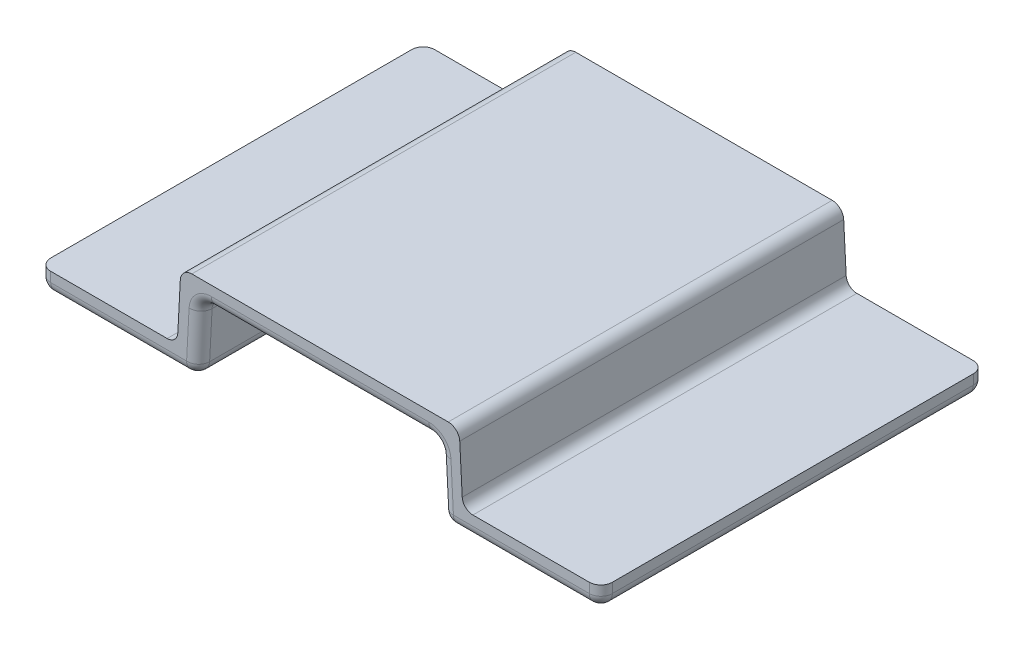
SolidWorks part; units mm, degrees
ref_plane "Front Plane" through (0, 0, 0) normal (0, 0, 1) x (1, 0, 0)
ref_plane "Top Plane" through (0, 0, 0) normal (0, 1, 0) x (1, 0, 0)
ref_plane "Right Plane" through (0, 0, 0) normal (1, 0, 0) x (0, 0, -1)
sketch "Sketch1" plane through (0, 0, 0) normal (0, 0, 1) x (1, 0, 0)
  line L0 (-329.1, -55) -> (-329.1, -80)
  line L1 (-329.1, -80) -> (-156.3657, -80)
  line L2 (-142.8842, -67.2065) -> (-139.9829, -11.8458)
  line L3 (-127.5, 0) -> (127.5, 0)
  line L4 (-329.1, -55) -> (-179.1409, -55)
  line L5 (-166.658, -43.1542) -> (-163.7566, 12.2065)
  line L6 (-150.2751, 25) -> (150.2751, 25)
  line L8 (0, 54.7842) -> (0, -49.5051) construction
  line L9 (166.658, -43.1542) -> (163.7566, 12.2065)
  line L10 (329.1, -55) -> (179.1409, -55)
  line L11 (142.8842, -67.2065) -> (139.9829, -11.8458)
  line L12 (329.1, -80) -> (156.3657, -80)
  line L13 (329.1, -55) -> (329.1, -80)
  arc A0 (-156.3657, -80) -> (-142.8842, -67.2065) centre (-156.3657, -66.5) ccw
  arc A1 (-179.1409, -55) -> (-166.658, -43.1542) centre (-179.1409, -42.5) ccw
  arc A2 (-163.7566, 12.2065) -> (-150.2751, 25) centre (-150.2751, 11.5) cw
  arc A4 (139.9829, -11.8458) -> (127.5, 0) centre (127.5, -12.5) ccw
  arc A5 (163.7566, 12.2065) -> (150.2751, 25) centre (150.2751, 11.5) ccw
  arc A6 (179.1409, -55) -> (166.658, -43.1542) centre (179.1409, -42.5) cw
  arc A7 (156.3657, -80) -> (142.8842, -67.2065) centre (156.3657, -66.5) cw
  arc A8 (-139.9829, -11.8458) -> (-127.5, 0) centre (-127.5, -12.5) cw
  point P9 (0, 25)
  point P10 (0, 0)
  dimension "D7" = 13.5
  dimension "D8" = 12.5
  dimension "D9" = 13.5
  dimension "D11" = 25
  dimension "D2" = 12.5
  dimension "D12" = 12.5
  dimension "D1" = 25
  dimension "D3" = 25
  dimension "D4" = 93
  dimension "D5" = 329.1
  dimension "D6" = 105
  dimension "D10" = 127.5
extrude "Boss-Extrude1" add sketch "Sketch1" along normal blind 225 and the other way blind 225
fillet "Fillet1" radius 13.5 19 edges at (242.7329, -80, -225) (147.0729, -76.2926, -225) (141.4335, -39.5262, -225) (136.1044, -3.4328, -225) (0, 0, -225) (-136.1044, -3.4328, -225) (-141.4335, -39.5262, -225) (-147.0729, -76.2926, -225) (242.7329, -80, 225) (147.0729, -76.2926, 225) (141.4335, -39.5262, 225) (136.1044, -3.4328, 225) (0, 0, 225) (-136.1044, -3.4328, 225) (-141.4335, -39.5262, 225) (-147.0729, -76.2926, 225) (-242.7329, -80, -225) (-329.1, -80, 0) (-242.7329, -80, 225)
fillet "Fillet2" radius 13.5 5 edges at (329.1, -60.75, -225) (329.1, -76.0459, -221.0459) (329.1, -60.75, 225) (329.1, -76.0459, 221.0459) (329.1, -80, 0)
fillet "Fillet3" radius 13.5 4 edges at (-325.1459, -76.0459, -221.0459) (-325.1459, -76.0459, 221.0459) (-329.1, -60.75, -225) (-329.1, -60.75, 225)
